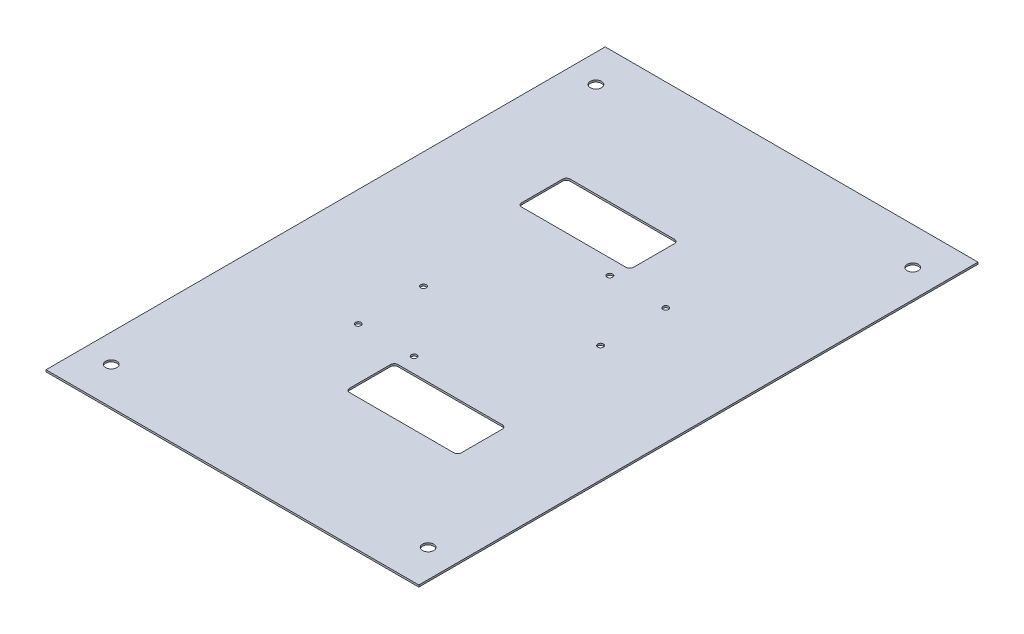
SolidWorks part; units mm, degrees
ref_plane "Plan de face" through (0, 0, 0) normal (0, 0, 1) x (1, 0, 0)
ref_plane "Plan de dessus" through (0, 0, 0) normal (0, 1, 0) x (1, 0, 0)
ref_plane "Plan de droite" through (0, 0, 0) normal (1, 0, 0) x (0, 0, -1)
sketch "Esquisse1" plane through (0, 0, 0) normal (0, 1, 0) x (1, 0, 0)
  line L0 (-2, -76.175) -> (42, -76.175) construction
  line L1 (-100, -150) -> (100, -150)
  line L2 (-100, -150) -> (-100, 150)
  line L3 (-100, 150) -> (100, 150)
  line L4 (100, -150) -> (100, 150)
  line L5 (-100, -150) -> (100, 150) construction
  line L6 (-100, 150) -> (100, -150) construction
  line L7 (-8, -53.175) -> (48, -53.175)
  line L8 (-10, -55.175) -> (-10, -77.175)
  line L9 (-8, -79.175) -> (48, -79.175)
  line L10 (50, -55.175) -> (50, -77.175)
  line L11 (47, -56.175) -> (-7, -56.175) construction
  line L12 (0, 0) -> (0, -150) construction
  line L13 (47, -150) -> (47, -53.175) construction
  line L14 (100, 0) -> (-100, 0) construction
  line L15 (-7, -53.175) -> (-7, -150) construction
  line L16 (0, 150) -> (0, 0) construction
  line L17 (7, 76.175) -> (-47, 76.175) construction
  line L18 (-48, 79.175) -> (8, 79.175)
  line L19 (-50, 77.175) -> (-50, 55.175)
  line L20 (-48, 53.175) -> (8, 53.175)
  line L21 (10, 77.175) -> (10, 55.175)
  line L22 (-47, 56.175) -> (7, 56.175) construction
  line L23 (-47, 56.175) -> (-47, 150) construction
  line L25 (7, 56.175) -> (7, 150) construction
  arc A0 (48, -79.175) -> (50, -77.175) centre (48, -77.175) ccw
  arc A1 (50, -55.175) -> (48, -53.175) centre (48, -55.175) ccw
  arc A2 (-8, -53.175) -> (-10, -55.175) centre (-8, -55.175) ccw
  arc A3 (-10, -77.175) -> (-8, -79.175) centre (-8, -77.175) ccw
  arc A4 (10, 55.175) -> (8, 53.175) centre (8, 55.175) cw
  arc A5 (10, 77.175) -> (8, 79.175) centre (8, 77.175) ccw
  arc A6 (-48, 79.175) -> (-50, 77.175) centre (-48, 77.175) ccw
  arc A7 (-50, 55.175) -> (-48, 53.175) centre (-48, 55.175) ccw
  circle A8 centre (-37.5, -45) radius 1.5
  circle A9 centre (-7.5, -45) radius 1.5
  circle A10 centre (-37.5, -10) radius 1.5
  circle A11 centre (37.5, 10) radius 1.5
  circle A12 centre (37.5, 45) radius 1.5
  circle A13 centre (7.5, 45) radius 1.5
  circle A14 centre (85, 130) radius 3
  circle A15 centre (-85, 130) radius 3
  circle A16 centre (85, -130) radius 3
  circle A17 centre (-85, -130) radius 3
  point P0 (0, 0)
  dimension "D11" = 2
  dimension "D12" = 3
  dimension "D13" = 3
  dimension "D14" = 3
  dimension "D15" = 3
  dimension "D16" = 3
  dimension "D17" = 3
  dimension "D18" = 6
  dimension "D20" = 130
  dimension "D19" = 85
  dimension "D1" = 200
  dimension "D2" = 300
  dimension "D3" = 3
  dimension "D4" = 3
  dimension "D5" = 3
  dimension "D6" = 3
  dimension "D7" = 3
  dimension "D8" = 3
  dimension "D9" = 3
  dimension "D10" = 3
extrude "Boss.-Extru.1" add sketch "Esquisse1" along normal blind 1
